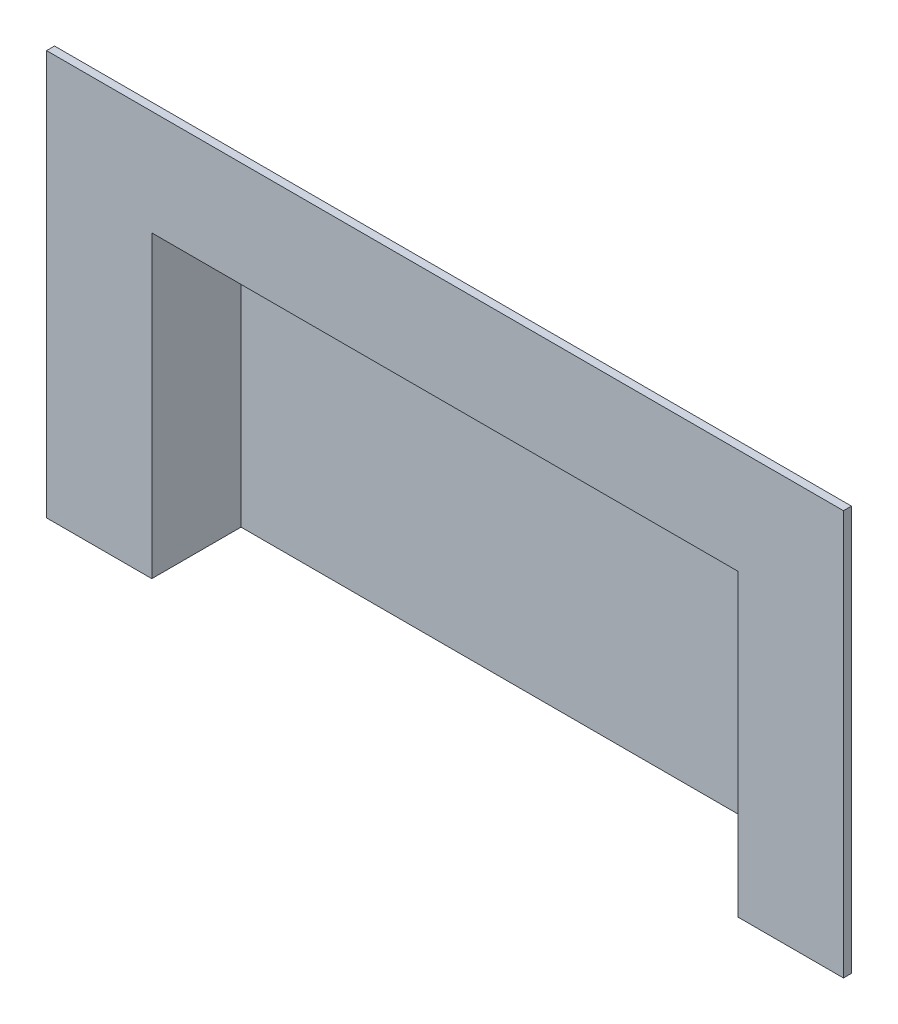
SolidWorks part; units mm, degrees
material "6063-O"
ref_plane "Front Plane" through (0, 0, 0) normal (0, 0, 1) x (1, 0, 0)
ref_plane "Top Plane" through (0, 0, 0) normal (0, 1, 0) x (1, 0, 0)
ref_plane "Right Plane" through (0, 0, 0) normal (1, 0, 0) x (0, 0, -1)
sketch "Sketch1" plane through (0, 0, 0) normal (0, 0, 1) x (1, 0, 0)
  line L1 (-48, -24.5) -> (48, -24.5)
  line L2 (-48, -24.5) -> (-48, 24.5)
  line L3 (-48, 24.5) -> (48, 24.5)
  line L4 (48, -24.5) -> (48, 24.5)
  line L5 (-48, -24.5) -> (48, 24.5) construction
  line L6 (-48, 24.5) -> (48, -24.5) construction
  point P0 (0, 0)
  dimension "D1" = 49
  dimension "D2" = 96
extrude "Boss-Extrude1" add sketch "Sketch1" along normal blind 15.494
sketch "Sketch2" plane through (0, 0, 15.494) normal (0, 0, 1) x (1, 0, 0)
  line L0 (-48, -24.5) -> (48, -24.5) construction
  line L1 (-63.5, -24.5) -> (63.5, -24.5)
  line L2 (-63.5, -24.5) -> (-63.5, 40)
  line L3 (-63.5, 40) -> (63.5, 40)
  line L4 (63.5, -24.5) -> (63.5, 40)
  line L9 (48, 24.5) -> (-48, 24.5) construction
  point P6 (0, 40)
  dimension "D1" = 127
  dimension "D2" = 15.5
extrude "Boss-Extrude2" add sketch "Sketch2" against normal blind 1.27
shell "Shell1" thickness 1.27 removed face at (0, -24.5, 10.9855) removed face at (0, 7.75, 15.494)
